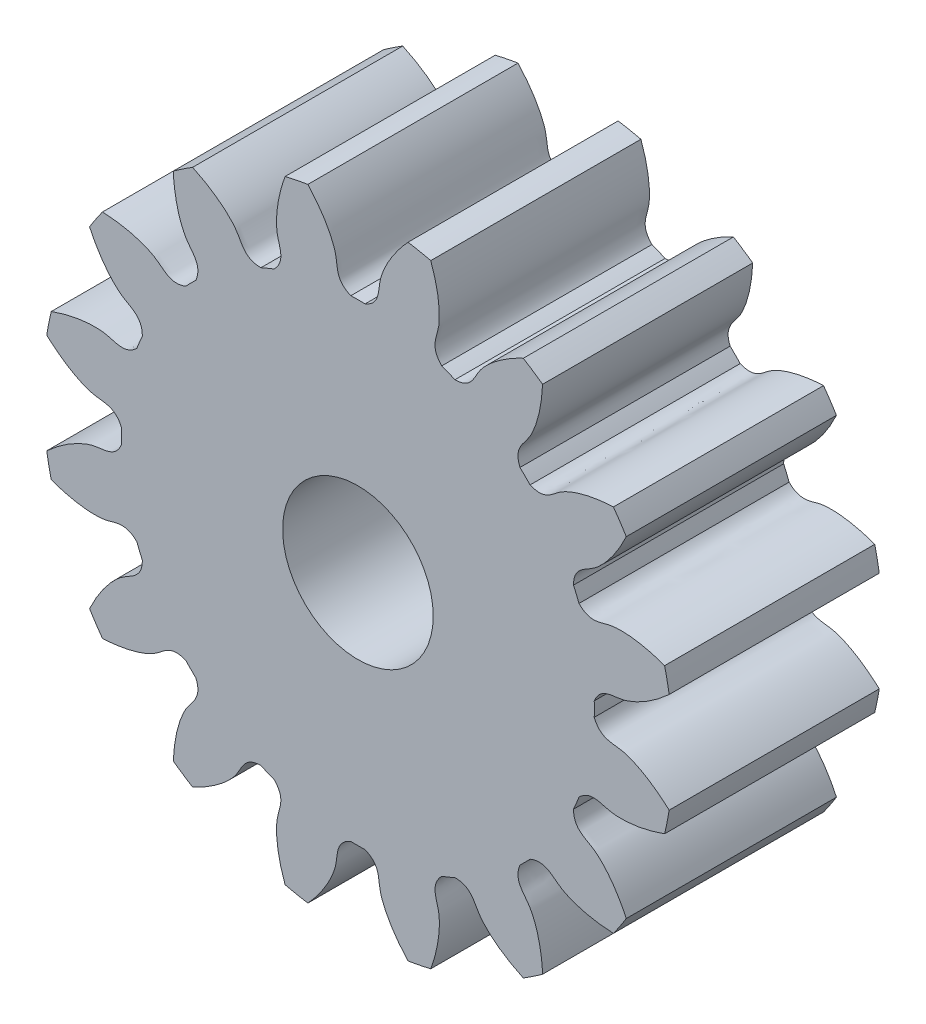
SolidWorks part; units mm, degrees
ref_plane "前视基准面" through (0, 0, 0) normal (0, 0, 1) x (1, 0, 0)
ref_plane "上视基准面" through (0, 0, 0) normal (0, 1, 0) x (1, 0, 0)
ref_plane "右视基准面" through (0, 0, 0) normal (1, 0, 0) x (0, 0, -1)
other "Configuration Table"
sketch "草图1" plane through (0, 0, 0) normal (0, 0, 1) x (1, 0, 0)
  circle A0 centre (0, 0) radius 4.5
extrude "凸台-拉伸1" add sketch "草图1" along normal blind 3
ref_axis "基准轴1" through (0, 0, 3) along (0, 0, -1)
sketch "草图2" plane through (0, 0, 0) normal (0, 0, 1) x (1, 0, 0)
  line L0 (0, 0) -> (0, 4.5) construction
  circle A0 centre (0, 0) radius 4.5 construction
  arc A1 (0.1017, 3.3735) -> (-0.1017, 3.3735) centre (0, 0) ccw
  arc A2 (1.5609, 5.0814) -> (-1.5609, 5.0814) centre (0, 0) ccw
  spline S0 degree 3 poles (0.1017, 3.3735) (0.3209, 3.4651) (0.2847, 3.6353) (0.3224, 3.7934) (0.3256, 3.8058) (0.3295, 3.8195) (0.334, 3.8346) (0.3394, 3.8511) (0.3455, 3.8688) (0.3526, 3.8879) (0.3605, 3.9082) (0.3695, 3.9297) (0.3794, 3.9524) (0.3905, 3.9763) (0.4027, 4.0013) (0.4161, 4.0274) (0.4307, 4.0545) (0.4466, 4.0827) (0.4638, 4.1118) (0.4823, 4.1419) (0.5023, 4.1728) (0.5238, 4.2046) (0.5467, 4.2372) (0.5712, 4.2705) (0.5973, 4.3045) (0.6249, 4.3392) (0.6543, 4.3744) (0.6853, 4.4102) (0.718, 4.4465) (0.7524, 4.4833) (0.7887, 4.5204) (0.8267, 4.5578) (0.8666, 4.5955) (0.9084, 4.6334) (0.952, 4.6715) (0.9975, 4.7096) (1.045, 4.7478) (1.0944, 4.7859) (1.1457, 4.8239) (1.1991, 4.8618) (1.2544, 4.8994) (1.3117, 4.9367) (1.3711, 4.9737) (1.4537, 5.023) (1.5175, 5.0584) (1.5609, 5.0814) knots 0 0 0 0 0.200958 0.205848 0.21139 0.217584 0.224431 0.231929 0.240079 0.248881 0.258335 0.268441 0.2792 0.29061 0.302672 0.315386 0.328753 0.342771 0.357441 0.372764 0.388738 0.405364 0.422643 0.440573 0.459155 0.47839 0.498276 0.518814 0.540005 0.561847 0.584342 0.607488 0.631287 0.655737 0.68084 0.706594 0.733001 0.760059 0.78777 0.816132 0.845147 0.874814 0.905132 0.936103 1 1 1 1
  spline S1 degree 3 poles (-0.1017, 3.3735) (-0.3209, 3.4651) (-0.2847, 3.6353) (-0.3224, 3.7934) (-0.3256, 3.8058) (-0.3295, 3.8195) (-0.334, 3.8346) (-0.3394, 3.8511) (-0.3455, 3.8688) (-0.3526, 3.8879) (-0.3605, 3.9082) (-0.3695, 3.9297) (-0.3794, 3.9524) (-0.3905, 3.9763) (-0.4027, 4.0013) (-0.4161, 4.0274) (-0.4307, 4.0545) (-0.4466, 4.0827) (-0.4638, 4.1118) (-0.4823, 4.1419) (-0.5023, 4.1728) (-0.5238, 4.2046) (-0.5467, 4.2372) (-0.5712, 4.2705) (-0.5973, 4.3045) (-0.6249, 4.3392) (-0.6543, 4.3744) (-0.6853, 4.4102) (-0.718, 4.4465) (-0.7524, 4.4833) (-0.7887, 4.5204) (-0.8267, 4.5578) (-0.8666, 4.5955) (-0.9084, 4.6334) (-0.952, 4.6715) (-0.9975, 4.7096) (-1.045, 4.7478) (-1.0944, 4.7859) (-1.1457, 4.8239) (-1.1991, 4.8618) (-1.2544, 4.8994) (-1.3117, 4.9367) (-1.3711, 4.9737) (-1.4537, 5.023) (-1.5175, 5.0584) (-1.5609, 5.0814) knots 0 0 0 0 0.200958 0.205848 0.21139 0.217584 0.224431 0.231929 0.240079 0.248881 0.258335 0.268441 0.2792 0.29061 0.302672 0.315386 0.328753 0.342771 0.357441 0.372764 0.388738 0.405364 0.422643 0.440573 0.459155 0.47839 0.498276 0.518814 0.540005 0.561847 0.584342 0.607488 0.631287 0.655737 0.68084 0.706594 0.733001 0.760059 0.78777 0.816132 0.845147 0.874814 0.905132 0.936103 1 1 1 1
extrude "切除-拉伸1" cut sketch "草图2" along normal through all
pattern_circular "阵列(圆周)1" count 16 every 22.5 about axis through (0, 0, 3) along (0, 0, -1) of "切除-拉伸1"
sketch "草图3" plane through (0, 0, 0) normal (0, 0, 1) x (1, 0, 0)
  circle A0 centre (0, 0) radius 4 construction
  dimension "Dn" = 8
sketch "草图4" plane through (0, 0, 3) normal (0, 0, 1) x (1, 0, 0)
  circle A0 centre (0, 0) radius 1.075
  dimension "D1" = 2.15
extrude "切除-拉伸2" cut sketch "草图4" against normal blind 10
